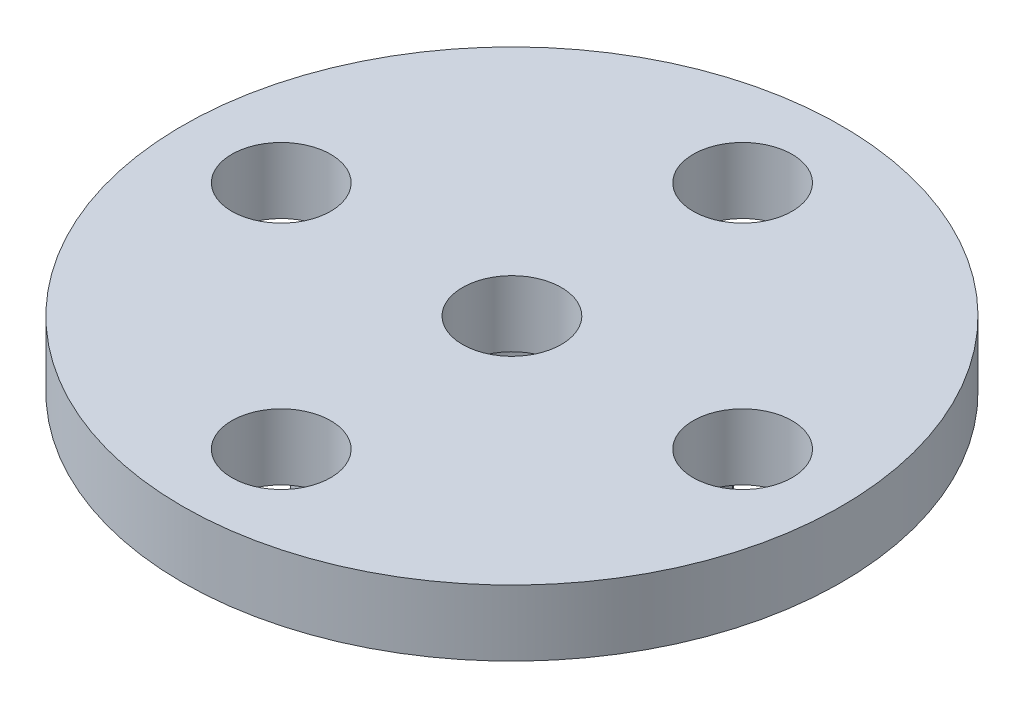
SolidWorks part; units mm, degrees
ref_plane "Front Plane" through (0, 0, 0) normal (0, 0, 1) x (1, 0, 0)
ref_plane "Top Plane" through (0, 0, 0) normal (0, 1, 0) x (1, 0, 0)
ref_plane "Right Plane" through (0, 0, 0) normal (1, 0, 0) x (0, 0, -1)
sketch "Sketch1" plane through (0, 0, 0) normal (0, 1, 0) x (1, 0, 0)
  circle A0 centre (0, 0) radius 10
  circle A1 centre (0, 0) radius 7 construction
  circle A2 centre (0, 0) radius 2.9
  circle A3 centre (0, 0) radius 4.75
  circle A4 centre (0, 0) radius 1.5
  circle A5 centre (0, -7) radius 1.5
  circle A6 centre (-7, 0) radius 1.5
  circle A7 centre (0, 7) radius 1.5
  circle A8 centre (7, 0) radius 1.5
  point P18 (0, 0)
  dimension "D1" = 20
  dimension "D2" = 14
  dimension "D3" = 9.5
  dimension "D4" = 5.8
  dimension "D5" = 3
  dimension "D6" = 3
  dimension "D7" = 4
extrude "Boss-Extrude1" add sketch "Sketch1" along normal blind 2 contours A0 A8 A7 A6 A5 A3 | A3 A2 | A2 A4 region at (-9.7172, 0, 0) region at (-2.818, 0, 0) region at (-4.6156, 0, 0)
extrude "Boss-Extrude2" add sketch "Sketch1<3>" against normal blind 3 contours A3 A2 region at (-4.6156, 0, 0)
sketch "Sketch1<3>" plane through (0, 0, 0) normal (0, 1, 0) x (1, 0, 0) same geometry as "Sketch1"
